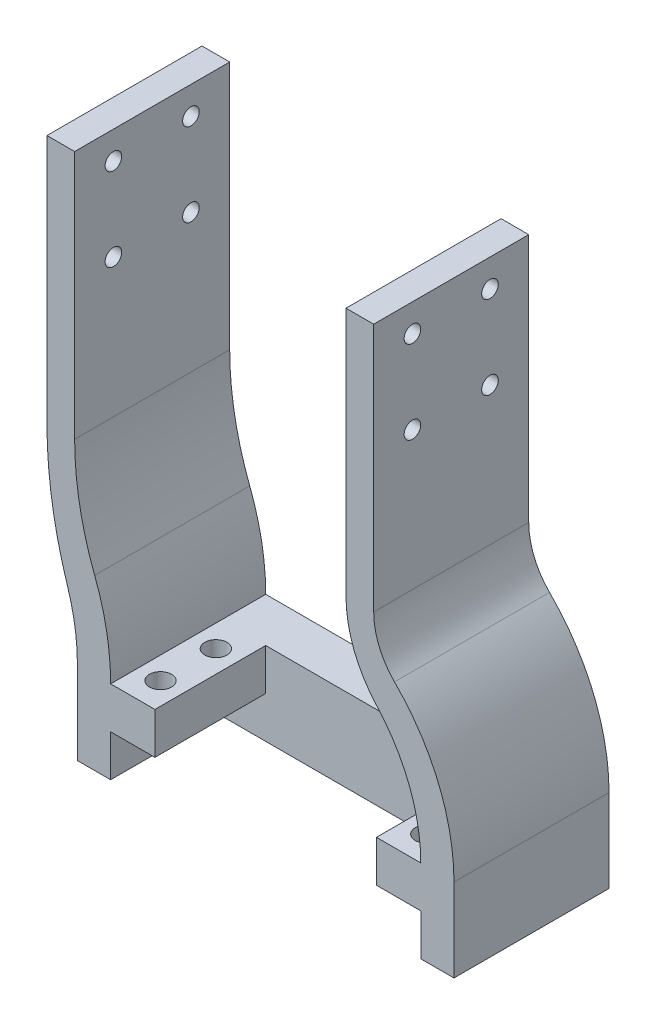
SolidWorks part; units mm, degrees
note: The reader was unsure of these and kept them because the rebuilt part matched: shared geometry of "Sketch1<5>".
ref_plane "Front Plane" through (0, 0, 0) normal (0, 0, 1) x (1, 0, 0)
ref_plane "Top Plane" through (0, 0, 0) normal (0, 1, 0) x (1, 0, 0)
ref_plane "Right Plane" through (0, 0, 0) normal (1, 0, 0) x (0, 0, -1)
sketch "Sketch1" plane through (0, 0, 0) normal (0, 1, 0) x (1, 0, 0)
  line L0 (6, -8) -> (62, -8)
  line L1 (0, 0) -> (68, 0)
  line L2 (0, 0) -> (0, -28)
  line L3 (0, -28) -> (68, -28)
  line L4 (68, 0) -> (68, -28)
  line L5 (6, 0) -> (14, 0)
  line L6 (6, 0) -> (6, -28)
  line L7 (6, -28) -> (14, -28)
  line L8 (14, 0) -> (14, -28)
  line L9 (54, 0) -> (62, 0)
  line L10 (54, 0) -> (54, -28)
  line L11 (54, -28) -> (62, -28)
  line L12 (62, 0) -> (62, -28)
  circle A0 centre (10, -23) radius 2
  circle A1 centre (10, -13) radius 2
  circle A2 centre (58, -13) radius 2
  circle A3 centre (58, -23) radius 2
  dimension "D7" = 4
  dimension "D8" = 4
  dimension "D9" = 4
  dimension "D10" = 4
  dimension "D1" = 68
  dimension "D2" = 28
  dimension "D3" = 6
  dimension "D4" = 8
  dimension "D5" = 6
  dimension "D6" = 8
  dimension "D11" = 4
  dimension "D12" = 4
  dimension "D13" = 5
  dimension "D14" = 10
  dimension "D15" = 5
  dimension "D16" = 4
  dimension "D17" = 4
  dimension "D18" = 10
  dimension "D19" = 8
extrude "Boss-Extrude1" add sketch "Sketch1" against normal blind 15 contours L6 L1 L2 L3 | L8 L1 L6 L0 | L10 L1 L8 L0 | L12 L1 L10 L0 | L1 L12 L3 L4
extrude "Boss-Extrude2" add sketch "Sketch1<5>" against normal blind 7.5 contours L8 L0 L6 L3 A1 A0 | L12 L0 L10 L3 A3 A2
sketch "Sketch1<5>" plane through (0, 0, 0) normal (0, 1, 0) x (1, 0, 0) same geometry as "Sketch1"
sketch "Sketch2" plane through (0, 0, 28) normal (0, 0, 1) x (1, 0, 0)
  line L0 (-0.5, 80) -> (48.5, 80) construction
  line L1 (-5.5, 80) -> (-0.5, 80)
  line L2 (-5.5, 80) -> (-5.5, 35)
  line L3 (-5.5, 35) -> (-0.5, 35)
  line L4 (-0.5, 80) -> (-0.5, 35)
  line L5 (48.5, 80) -> (53.5, 80)
  line L6 (48.5, 80) -> (48.5, 35)
  line L7 (48.5, 35) -> (53.5, 35)
  line L8 (53.5, 80) -> (53.5, 35)
  line L9 (14, 0) -> (54, 0) construction
  line L10 (14, 0) -> (54, 0)
  line L11 (34, 0) -> (34, 34.6923) construction
  line L12 (6, -7.5) -> (6, 0)
  line L13 (0, 0) -> (14, 0) construction
  line L14 (62, -7.5) -> (62, 0)
  line L15 (54, 0) -> (68, 0) construction
  line L16 (68, -15) -> (68, 0) construction
  line L18 (0, -15) -> (0, 0) construction
  line L21 (62, 0) -> (68, 0)
  line L22 (6, 0) -> (0, 0)
  arc A0 (53.5, 35) -> (57.2563, 25.933) centre (66.321, 35) ccw
  arc A1 (57.2563, 25.933) -> (68, 0) centre (31.3297, 0) cw
  arc A2 (48.5, 35) -> (54.0559, 20.5958) centre (69.95, 35) ccw
  arc A3 (54.0559, 20.5958) -> (62, 0) centre (31.3297, 0) cw
  arc A4 (-5.5, 35) -> (-1.794, 11.416) centre (71.3929, 35) ccw
  arc A5 (-1.794, 11.416) -> (0, 0) centre (-37.2208, 0) cw
  arc A6 (-0.5, 35) -> (3.118, 15.5182) centre (53.76, 35) ccw
  arc A7 (3.118, 15.5182) -> (6, 0) centre (-37.2208, 0) cw
  point P29 (24, 80)
  point P43 (0.5, 24.6337)
  point P44 (57.1631, 14.0675)
  point P45 (60.2838, 20.0049)
  point P46 (55.9058, 17.0639)
  point P47 (58.5018, 24.6337)
  dimension "D1" = 5
  dimension "D2" = 5
  dimension "D3" = 45
  dimension "D4" = 45
  dimension "D5" = 10
  dimension "D6" = 49
  dimension "D7" = 80
extrude "Boss-Extrude3" add sketch "Sketch2" against normal up to surface (28 mm away) up to face at (34, -7.5, 0)
sketch "Sketch3" plane through (53.5, 0, 0) normal (1, 0, 0) x (0, 0, -1)
  line L0 (0, 80) -> (-28, 80) construction
  line L1 (-28, 80) -> (-28, 35) construction
  line L2 (-14, 80) -> (-14, 48.4886) construction
  circle A0 centre (-21, 75) radius 1.5
  circle A1 centre (-21, 60) radius 1.5
  circle A2 centre (-7, 60) radius 1.5
  circle A3 centre (-7, 75) radius 1.5
  dimension "D1" = 3
  dimension "D4" = 3
  dimension "D2" = 5
  dimension "D3" = 7
  dimension "D5" = 7
  dimension "D6" = 15
extrude "Cut-Extrude1" cut sketch "Sketch3" against normal up to surface (59 mm away) up to face at (-5.5, 57.5, 14)
